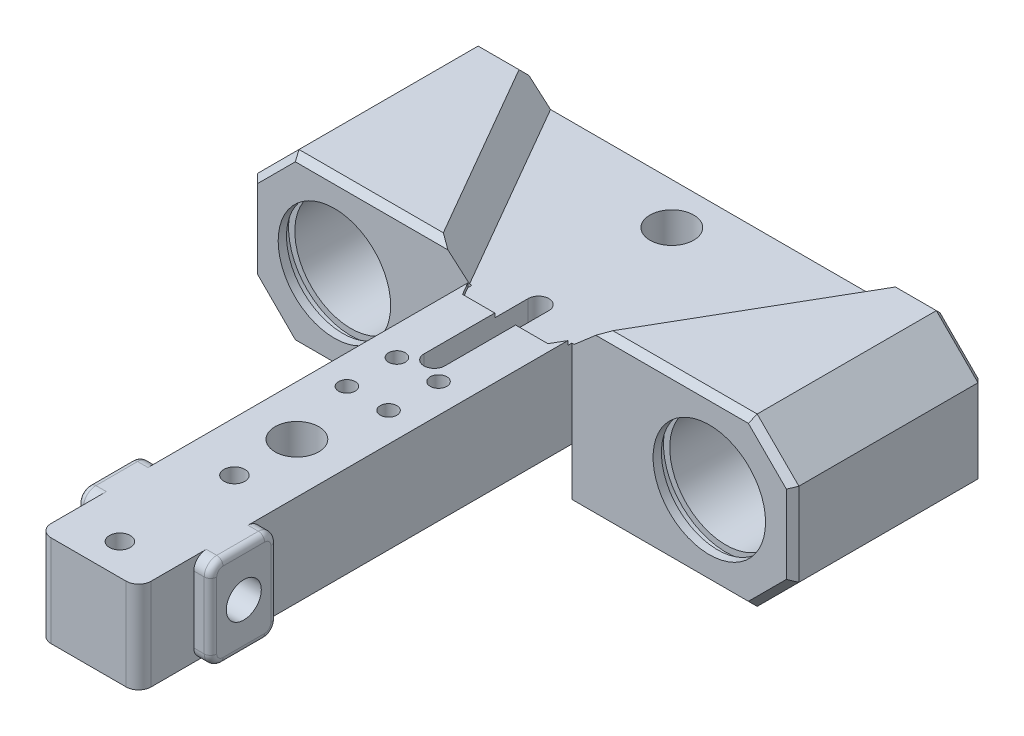
SolidWorks part; units mm, degrees
ref_plane "Front Plane" through (0, 0, 0) normal (0, 0, 1) x (1, 0, 0)
ref_plane "Top Plane" through (0, 0, 0) normal (0, 1, 0) x (1, 0, 0)
ref_plane "Right Plane" through (0, 0, 0) normal (1, 0, 0) x (0, 0, -1)
sketch "Sketch1" plane through (0, 0, 0) normal (0, 0, 1) x (1, 0, 0)
  line L1 (-65, -20) -> (65, -20)
  line L2 (-65, -20) -> (-65, 20)
  line L3 (-65, 20) -> (65, 20)
  line L4 (65, -20) -> (65, 20)
  line L5 (-65, -20) -> (65, 20) construction
  line L6 (-65, 20) -> (65, -20) construction
  point P0 (0, 0)
  dimension "D1" = 130
  dimension "D2" = 40
extrude "Boss-Extrude1" add sketch "Sketch1" along normal blind 125
sketch "Sketch2" plane through (0, 0, 125) normal (0, 0, 1) x (1, 0, 0)
  circle A0 centre (-45, 0) radius 13.5
  circle A1 centre (45, 0) radius 13.5
  dimension "D1" = 27
  dimension "D2" = 27
  dimension "D3" = 45
  dimension "D4" = 45
extrude "Cut-Extrude1" cut sketch "Sketch2" against normal blind 130
sketch "Sketch3" plane through (0, 0, 125) normal (0, 0, 1) x (1, 0, 0)
  line L0 (-65, -20) -> (65, -20) construction
  line L1 (-12, -20) -> (12, -20)
  line L2 (-12, -20) -> (-12, -7)
  line L3 (-12, -7) -> (12, -7)
  line L4 (12, -20) -> (12, -7)
  dimension "D1" = 13
  dimension "D2" = 24
  dimension "D3" = 12
extrude "Cut-Extrude2" cut sketch "Sketch3" against normal blind 125
sketch "Sketch4" plane through (0, 0, 125) normal (0, 0, 1) x (1, 0, 0)
  line L0 (65, 20) -> (-65, 20) construction
  line L1 (-10.25, 20) -> (10.25, 20)
  line L2 (-10.25, 20) -> (-10.25, 15)
  line L3 (-10.25, 15) -> (10.25, 15)
  line L4 (10.25, 20) -> (10.25, 15)
  dimension "D1" = 5
  dimension "D2" = 20.5
  dimension "D3" = 10.25
extrude "Cut-Extrude3" cut sketch "Sketch4" against normal blind 125
sketch "Sketch5" plane through (0, 15, 0) normal (0, 1, 0) x (1, 0, 0)
  line L1 (-10.25, 0) -> (10.25, 0) construction
  circle A0 centre (0, -10) radius 2.75
  circle A1 centre (0, -100) radius 2.75
  dimension "D1" = 5.5
  dimension "D2" = 5.5
  dimension "D3" = 90
  dimension "D4" = 10
extrude "Cut-Extrude4" cut sketch "Sketch5" against normal blind 40
sketch "Sketch6" plane through (0, 15, 0) normal (0, 1, 0) x (1, 0, 0)
  line L0 (0, -42) -> (0, -67) construction
  line L1 (2.5, -42) -> (2.5, -67)
  line L2 (-2.5, -42) -> (-2.5, -67)
  line L3 (-10.25, -125) -> (10.25, -125) construction
  line L4 (-5, -71) -> (5, -71) construction
  line L5 (-5, -71) -> (-5, -83) construction
  line L6 (-5, -83) -> (5, -83) construction
  line L7 (5, -71) -> (5, -83) construction
  arc A0 (2.5, -42) -> (-2.5, -42) centre (0, -42) ccw
  arc A1 (-2.5, -67) -> (2.5, -67) centre (0, -67) ccw
  circle A2 centre (-5, -71) radius 2
  circle A3 centre (5, -71) radius 2
  circle A4 centre (5, -83) radius 2
  circle A6 centre (-5, -83) radius 2
  point P3 (0, -54.5)
  dimension "D5" = 4
  dimension "D6" = 4
  dimension "D7" = 4
  dimension "D8" = 4
  dimension "D1" = 5
  dimension "D2" = 25
  dimension "D3" = 10
  dimension "D4" = 12
  dimension "D9" = 4
  dimension "D10" = 5
  dimension "D11" = 42
extrude "Cut-Extrude5" cut sketch "Sketch6" against normal blind 40
sketch "Sketch7" plane through (0, 15, 0) normal (0, 1, 0) x (1, 0, 0)
  circle A0 centre (0, -100) radius 5.25
  circle A1 centre (0, -10) radius 5.25
  dimension "D1" = 10.5
  dimension "D2" = 10.5
extrude "Cut-Extrude6" cut sketch "Sketch7" against normal blind 15
sketch "Sketch10" plane through (0, 0, 0) normal (0, 0, -1) x (-1, 0, 0)
  circle A0 centre (-45, 0) radius 15
  circle A1 centre (45, 0) radius 15
  circle A2 centre (45, 0) radius 13.5 construction
  circle A3 centre (-45, 0) radius 13.5 construction
  circle A4 centre (45, 0) radius 13.5
  circle A5 centre (-45, 0) radius 13.5
  dimension "D1" = 30
  dimension "D2" = 30
extrude "Cut-Extrude11" cut sketch "Sketch10" against normal blind 2 from offset 2 offset against normal yes
chamfer "Chamfer1" distance 10 angle 45 4 edges at (65, -20, 62.5) (65, 20, 62.5) (-65, -20, 62.5) (-65, 20, 62.5)
sketch "Sketch12" plane through (0, 0, 125) normal (0, 0, 1) x (1, 0, 0)
  line L0 (-12, -7) -> (-12, 15)
  line L1 (-12, 15) -> (-10.25, 15)
  line L2 (12, -7) -> (12, 15)
  line L3 (12, 15) -> (10.25, 15)
  line L4 (-10.25, 15) -> (-10.25, 20)
  line L5 (-10.25, 20) -> (-55, 20)
  line L6 (-55, 20) -> (-65, 10)
  line L7 (-65, 10) -> (-65, -10)
  line L8 (-65, -10) -> (-55, -20)
  line L9 (-55, -20) -> (-12, -20)
  line L10 (-12, -20) -> (-12, -7)
  line L11 (10.25, 15) -> (10.25, 20)
  line L12 (10.25, 20) -> (55, 20)
  line L13 (55, 20) -> (65, 10)
  line L14 (65, 10) -> (65, -10)
  line L15 (65, -10) -> (55, -20)
  line L16 (55, -20) -> (12, -20)
  line L17 (12, -20) -> (12, -7)
extrude "Cut-Extrude13" cut sketch "Sketch12" against normal blind 79
sketch "Sketch13" plane through (0, 0, 46) normal (0, 0, 1) x (1, 0, 0)
  circle A0 centre (-45, 0) radius 15
  circle A1 centre (45, 0) radius 15
  circle A2 centre (45, 0) radius 13.5 construction
  circle A3 centre (-45, 0) radius 13.5 construction
  circle A4 centre (45, 0) radius 13.5
  circle A5 centre (-45, 0) radius 13.5
  dimension "D1" = 30
  dimension "D2" = 30
extrude "Cut-Extrude14" cut sketch "Sketch13" against normal blind 2 from offset 2 offset against normal yes
sketch "Sketch14" plane through (0, 20, 0) normal (0, 1, 0) x (1, 0, 0)
  line L0 (-12, -125) -> (12, -125) construction
  line L1 (-10.25, -50) -> (10.25, -50)
  line L2 (12, -46) -> (12, -125) construction
  line L5 (-39.1175, 0) -> (-10.25, -50)
  line L6 (39.1175, 0) -> (10.25, -50)
  line L7 (-10.25, -46) -> (-10.25, 0) construction
  line L9 (0, -50) -> (0, -42.1441) construction
  line L10 (10.25, 0) -> (10.25, -46) construction
  line L16 (55, 0) -> (10.25, 0) construction
  line L18 (-10.25, 0) -> (-55, 0) construction
  line L19 (39.1175, 0) -> (10.25, 0)
  line L20 (10.25, 0) -> (-10.25, 0)
  line L21 (-10.25, 0) -> (-39.1175, 0)
  dimension "D2" = 75
  dimension "D3" = 12
  dimension "D4" = 0
  dimension "D5" = 30
  dimension "D6" = 30
extrude "Cut-Extrude16" cut sketch "Sketch14" against normal blind 6
chamfer "Chamfer2" distance 6 angle 45 2 edges at (-25.8385, 20, 23) (25.8385, 20, 23)
chamfer "Chamfer3" distance 1.5 angle 45 10 edges at (33.5, -20, 46) (60, -15, 46) (65, 0, 46) (60, 15, 46) (37.2438, 20, 46) (-33.5, -20, 46) (-60, -15, 46) (-65, 0, 46) (-60, 15, 46) (-37.2438, 20, 46)
chamfer "Chamfer4" distance 1.5 angle 45 10 edges at (-33.5, -20, 0) (-60, -15, 0) (-65, 0, 0) (-60, 15, 0) (-50.5229, 20, 0) (33.5, -20, 0) (60, -15, 0) (65, 0, 0) (60, 15, 0) (50.5229, 20, 0)
sketch "Sketch16" plane through (0, 0, 125) normal (0, 0, 1) x (1, 0, 0)
  line L4 (12, 15) -> (-12, 15)
  line L5 (-12, 15) -> (-12, -7)
  line L6 (-12, -7) -> (12, -7)
  line L7 (12, -7) -> (12, 15)
  line L8 (12, 15) -> (-12, 15)
  line L9 (-12, 15) -> (-12, -7)
  line L10 (-12, -7) -> (12, -7)
  line L11 (12, -7) -> (12, 15)
  dimension "D1" = 0
extrude "Boss-Extrude2" add sketch "Sketch16" along normal blind 25
sketch "Sketch17" plane through (0, 15, 0) normal (0, 1, 0) x (1, 0, 0)
  line L0 (12, -150) -> (-12, -150) construction
  circle A0 centre (0, -142.5) radius 2.5
  circle A1 centre (0, -115) radius 2.5
  dimension "D1" = 5
  dimension "D2" = 5
  dimension "D3" = 7.5
  dimension "D4" = 27.5
extrude "Cut-Extrude17" cut sketch "Sketch17" against normal blind 25
fillet "Fillet2" radius 3 2 edges at (-12, 4, 150) (12, 4, 150)
sketch "Sketch18" plane through (0, 15, 0) normal (0, 1, 0) x (1, 0, 0)
  line L0 (-12, -46.9689) -> (-12, -147) construction
  line L1 (-16, -120.75) -> (16, -120.75)
  line L2 (-16, -120.75) -> (-16, -136.75)
  line L3 (-16, -136.75) -> (16, -136.75)
  line L4 (16, -120.75) -> (16, -136.75)
  line L6 (0, -136.75) -> (0, -120.75) construction
  line L7 (9, -150) -> (-9, -150) construction
  dimension "D1" = 16
  dimension "D2" = 4
  dimension "D3" = 13.25
extrude "Boss-Extrude3" add sketch "Sketch18" against normal blind 22
sketch "Sketch19" plane through (-16, 0, 0) normal (-1, 0, 0) x (0, 0, 1)
  line L0 (120.75, -7) -> (120.75, 15) construction
  line L2 (120.75, 15) -> (136.75, 15) construction
  circle A0 centre (128.75, 4) radius 4.2
  dimension "D1" = 8.4
  dimension "D2" = 8
  dimension "D3" = 11
extrude "Cut-Extrude18" cut sketch "Sketch19" against normal blind 40
fillet "Fillet3" radius 3 8 edges at (14, -7, 120.75) (14, -7, 136.75) (-14, -7, 136.75) (-14, -7, 120.75) (14, 15, 136.75) (14, 15, 120.75) (-14, 15, 136.75) (-14, 15, 120.75)
fillet "Fillet4" radius 1.5 16 edges at (-16, 14.1213, 121.6287) (-16, 4, 120.75) (-16, -6.1213, 121.6287) (-16, -7, 128.75) (-16, -6.1213, 135.8713) (-16, 4, 136.75) (-16, 14.1213, 135.8713) (16, 14.1213, 135.8713) (16, 4, 136.75) (16, -6.1213, 135.8713) (16, -7, 128.75) (16, -6.1213, 121.6287) (16, 4, 120.75) (16, 14.1213, 121.6287) (-16, 15, 128.75) (16, 15, 128.75)
sketch "Sketch20" plane through (-16, 0, 0) normal (-1, 0, 0) x (0, 0, 1)
  circle A0 centre (128.75, 4) radius 5.75
  dimension "D1" = 11.5
extrude "Cut-Extrude19" cut sketch "Sketch20" against normal blind 11
